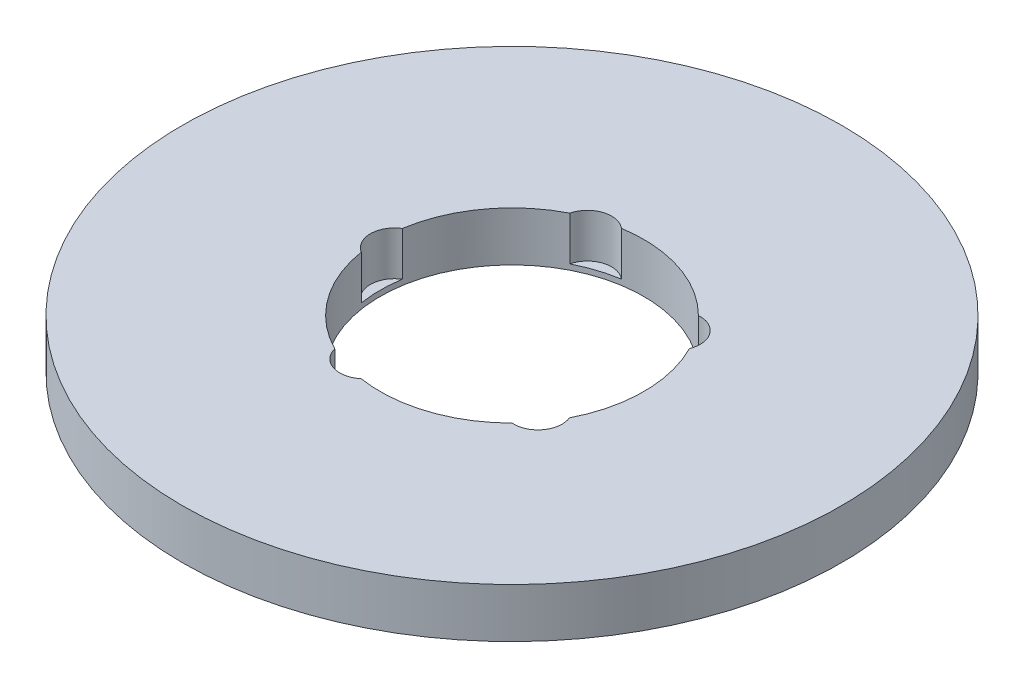
SolidWorks part; units mm, degrees
ref_plane "Front Plane" through (0, 0, 0) normal (0, 0, 1) x (1, 0, 0)
ref_plane "Top Plane" through (0, 0, 0) normal (0, 1, 0) x (1, 0, 0)
ref_plane "Right Plane" through (0, 0, 0) normal (1, 0, 0) x (0, 0, -1)
sketch "Sketch1" plane through (0, 0, 0) normal (0, 1, 0) x (1, 0, 0)
  circle A0 centre (0, 0) radius 100
  dimension "FLANGE_OD" = 200
extrude "Boss-Extrude1" add sketch "Sketch1" along normal blind 15
sketch "Sketch2" plane through (0, 0, 0) normal (0, 1, 0) x (1, 0, 0)
  circle A0 centre (0, 0) radius 40
  dimension "BORE_D" = 80
extrude "Cut-Extrude1" cut sketch "Sketch2" along normal through all
sketch "Sketch3" plane through (0, 15, 0) normal (0, 1, 0) x (1, 0, 0)
  circle A0 centre (0, 0) radius 35.6567 construction
  circle A1 centre (-35.6567, 0) radius 7.3165
  dimension "BOLT_D" = 14.6331
  dimension "BOLT_PCD" = 71.3133
extrude "Cut-Extrude2" cut sketch "Sketch3" against normal blind 13.3416
pattern_circular "CirPattern1" count 5 over 360 about axis through (0, 0, 0) along (0, 1, 0) of "Cut-Extrude2"
